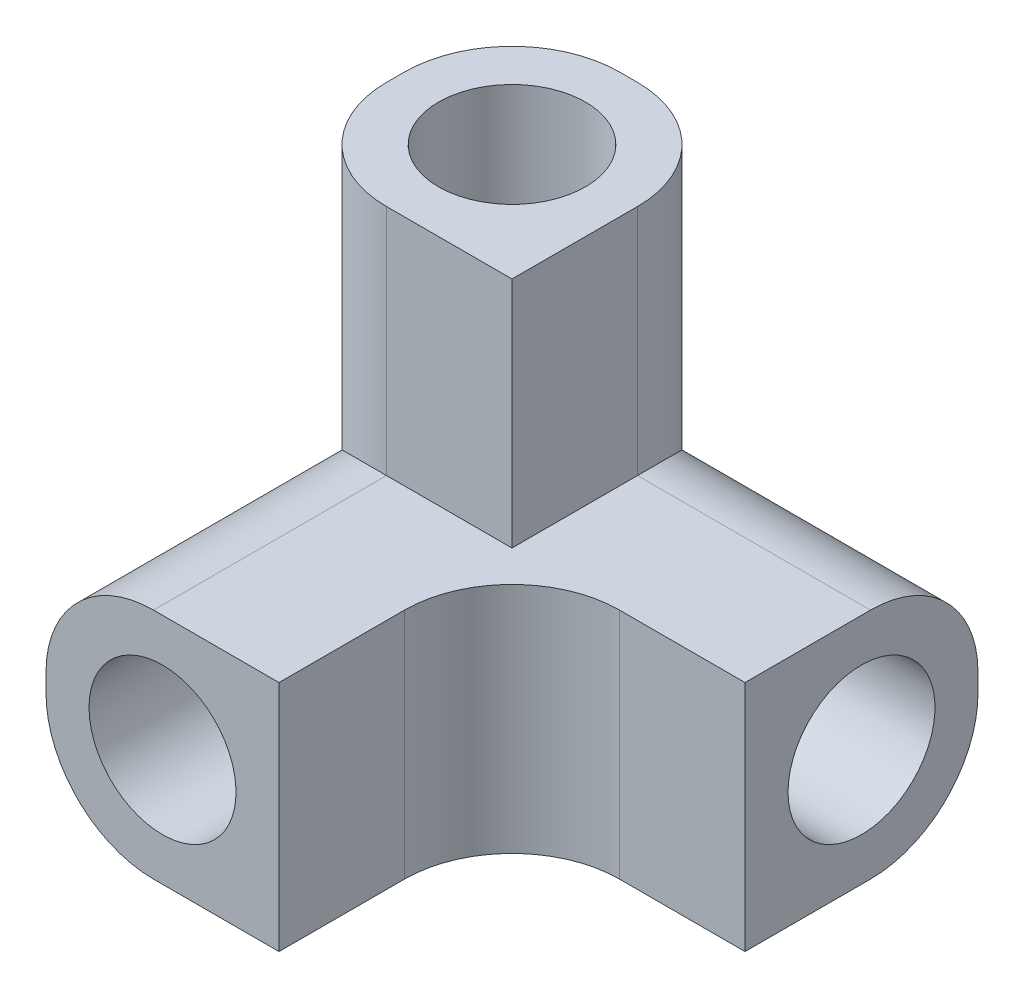
SolidWorks part; units mm, degrees
ref_plane "前视基准面" through (0, 0, 0) normal (0, 0, 1) x (1, 0, 0)
ref_plane "上视基准面" through (0, 0, 0) normal (0, 1, 0) x (1, 0, 0)
ref_plane "右视基准面" through (0, 0, 0) normal (1, 0, 0) x (0, 0, -1)
sketch "草图1" plane through (0, 0, 0) normal (0, 0, 1) x (1, 0, 0)
  line L1 (-11.8307, 8.0321) -> (-5.3307, 8.0321)
  line L2 (-11.8307, 8.0321) -> (-11.8307, 1.5321)
  line L3 (-11.8307, 1.5321) -> (-5.3307, 1.5321)
  line L4 (-5.3307, 8.0321) -> (-5.3307, 1.5321)
  line L5 (-11.8307, 8.0321) -> (-5.3307, 1.5321) construction
  line L6 (-11.8307, 1.5321) -> (-5.3307, 8.0321) construction
  circle A1 centre (-8.5807, 4.7821) radius 2.05
  dimension "D1" = 4.1
  dimension "D2" = 6.5
  dimension "D3" = 6.5
extrude "凸台-拉伸1" add sketch "草图1" along normal blind 6.5
sketch "草图2" plane through (-5.3307, 0, 0) normal (1, 0, 0) x (0, 0, -1)
  line L0 (-6.5, 8.0321) -> (0, 8.0321) construction
  line L1 (0, 1.5321) -> (6.5, 1.5321)
  line L2 (0, 1.5321) -> (0, 14.5321)
  line L3 (0, 14.5321) -> (6.5, 14.5321)
  line L4 (6.5, 1.5321) -> (6.5, 14.5321)
  dimension "D1" = 6.5
  dimension "D2" = 6.5
extrude "凸台-拉伸2" add sketch "草图2" against normal up to surface (6.5 mm away) up to face at (-11.8307, 4.7821, 3.25)
sketch "草图3" plane through (-5.3307, 0, 0) normal (1, 0, 0) x (0, 0, -1)
  line L0 (6.5, 8.0321) -> (0, 1.5321) construction
  line L1 (0, 8.0321) -> (6.5, 8.0321)
  line L2 (0, 8.0321) -> (0, 1.5321)
  line L3 (0, 1.5321) -> (6.5, 1.5321)
  line L4 (6.5, 8.0321) -> (6.5, 1.5321)
  line L5 (0, 8.0321) -> (6.5, 1.5321) construction
  circle A0 centre (3.25, 4.7821) radius 2.05
  point P8 (4, 4.0321)
  dimension "D1" = 4.1
extrude "凸台-拉伸3" add sketch "草图3" along normal blind 6.5
sketch "草图4" plane through (0, 14.5321, 0) normal (0, 1, 0) x (1, 0, 0)
  line L0 (-11.8307, 0) -> (-5.3307, 6.5) construction
  line L1 (-5.3307, 0) -> (-11.8307, 6.5) construction
  circle A0 centre (-8.5807, 3.25) radius 2.05
  point P10 (-9.3307, 4)
  dimension "D1" = 4.1
extrude "切除-拉伸1" cut sketch "草图4" against normal blind 8
fillet "圆角1" radius 3 7 edges at (-5.3307, 11.2821, -6.5) (-11.8307, 11.2821, 0) (-11.8307, 8.0321, 3.25) (-2.0807, 8.0321, -6.5) (-5.3307, 1.5321, -6.5) (-11.8307, 1.5321, 0) (-11.8307, 8.0321, -6.5)
fillet "圆角2" radius 3 1 edges at (-5.3307, 4.7821, 0)
